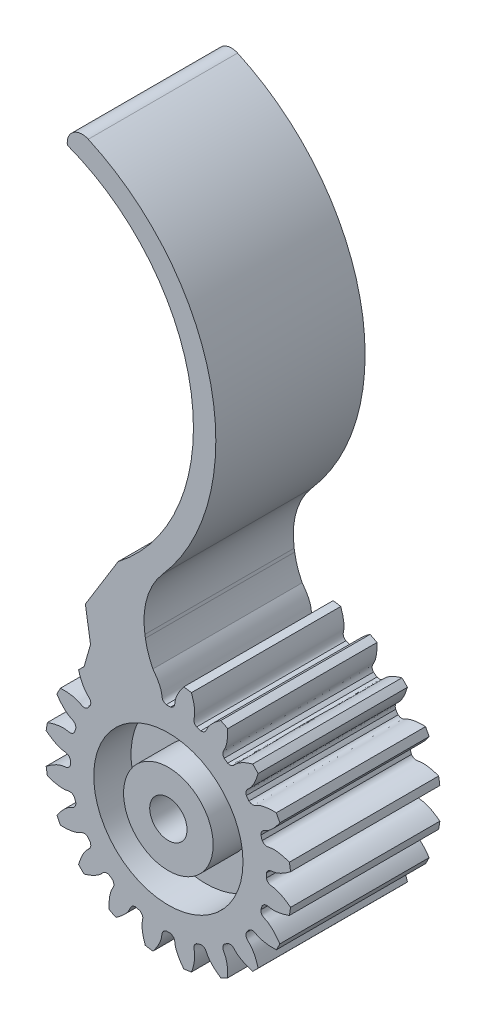
SolidWorks part; units mm, degrees
material "聚脂树脂"
ref_plane "前视基准面" through (0, 0, 0) normal (0, 0, 1) x (1, 0, 0)
ref_plane "上视基准面" through (0, 0, 0) normal (0, 1, 0) x (1, 0, 0)
ref_plane "右视基准面" through (0, 0, 0) normal (1, 0, 0) x (0, 0, -1)
other "Configuration Table"
sketch "草图1" plane through (0, 0, 0) normal (0, 0, 1) x (1, 0, 0)
  circle A0 centre (0, 0) radius 16.5
extrude "凸台-拉伸1" add sketch "草图1" along normal blind 20
ref_axis "基准轴1" through (0, 0, -1.5) along (0, 0, 1)
sketch "草图2" plane through (0, 0, 0) normal (0, 0, 1) x (1, 0, 0)
  line L0 (0, 0) -> (0, 16.5) construction
  circle A0 centre (0, 0) radius 16.5 construction
  arc A1 (0.29, 13.1218) -> (-0.29, 13.1218) centre (0, 0) ccw
  arc A2 (4.7717, 18.7474) -> (-4.7717, 18.7474) centre (0, 0) ccw
  spline S0 degree 3 poles (0.29, 13.1218) (0.9168, 13.3402) (0.8356, 13.7807) (0.9193, 14.205) (0.9283, 14.2463) (0.9395, 14.293) (0.9529, 14.3448) (0.969, 14.4018) (0.9878, 14.4638) (1.0095, 14.5309) (1.0345, 14.6028) (1.0629, 14.6795) (1.0948, 14.7608) (1.1305, 14.8467) (1.1702, 14.9371) (1.2141, 15.0317) (1.2623, 15.1305) (1.315, 15.2334) (1.3725, 15.3401) (1.4349, 15.4506) (1.5023, 15.5646) (1.575, 15.6821) (1.653, 15.8029) (1.7366, 15.9267) (1.826, 16.0534) (1.9211, 16.1829) (2.0223, 16.3149) (2.1296, 16.4493) (2.2432, 16.5859) (2.3632, 16.7244) (2.4897, 16.8646) (2.6229, 17.0065) (2.7628, 17.1496) (2.9095, 17.2939) (3.0632, 17.4391) (3.224, 17.585) (3.3918, 17.7313) (3.567, 17.8779) (3.7493, 18.0245) (3.9391, 18.1709) (4.1363, 18.3167) (4.4122, 18.5125) (4.6259, 18.6545) (4.7717, 18.7474) knots 0 0 0 0 0.165916 0.170906 0.176664 0.183189 0.190482 0.198542 0.207371 0.216967 0.22733 0.238462 0.250361 0.263027 0.276462 0.290664 0.305634 0.321371 0.337876 0.355149 0.37319 0.391998 0.411574 0.431917 0.453028 0.474907 0.497554 0.520968 0.54515 0.570099 0.595817 0.622302 0.649554 0.677575 0.706363 0.735918 0.766242 0.797333 0.829191 0.861818 0.895212 0.929373 1 1 1 1
  spline S1 degree 3 poles (-0.29, 13.1218) (-0.9168, 13.3402) (-0.8356, 13.7807) (-0.9193, 14.205) (-0.9283, 14.2463) (-0.9395, 14.293) (-0.9529, 14.3448) (-0.969, 14.4018) (-0.9878, 14.4638) (-1.0095, 14.5309) (-1.0345, 14.6028) (-1.0629, 14.6795) (-1.0948, 14.7608) (-1.1305, 14.8467) (-1.1702, 14.9371) (-1.2141, 15.0317) (-1.2623, 15.1305) (-1.315, 15.2334) (-1.3725, 15.3401) (-1.4349, 15.4506) (-1.5023, 15.5646) (-1.575, 15.6821) (-1.653, 15.8029) (-1.7366, 15.9267) (-1.826, 16.0534) (-1.9211, 16.1829) (-2.0223, 16.3149) (-2.1296, 16.4493) (-2.2432, 16.5859) (-2.3632, 16.7244) (-2.4897, 16.8646) (-2.6229, 17.0065) (-2.7628, 17.1496) (-2.9095, 17.2939) (-3.0632, 17.4391) (-3.224, 17.585) (-3.3918, 17.7313) (-3.567, 17.8779) (-3.7493, 18.0245) (-3.9391, 18.1709) (-4.1363, 18.3167) (-4.4122, 18.5125) (-4.6259, 18.6545) (-4.7717, 18.7474) knots 0 0 0 0 0.165916 0.170906 0.176664 0.183189 0.190482 0.198542 0.207371 0.216967 0.22733 0.238462 0.250361 0.263027 0.276462 0.290664 0.305634 0.321371 0.337876 0.355149 0.37319 0.391998 0.411574 0.431917 0.453028 0.474907 0.497554 0.520968 0.54515 0.570099 0.595817 0.622302 0.649554 0.677575 0.706363 0.735918 0.766242 0.797333 0.829191 0.861818 0.895212 0.929373 1 1 1 1
extrude "切除-拉伸1" cut sketch "草图2" along normal through all
pattern_circular "阵列(圆周)1" count 20 over 360 about axis through (0, 0, -1.5) along (0, 0, 1) of "切除-拉伸1"
sketch "草图3" plane through (0, 0, 0) normal (0, 0, 1) x (1, 0, 0)
  circle A0 centre (0, 0) radius 15 construction
  dimension "Dn" = 30
sketch "草图4" plane through (0, 0, 20) normal (0, 0, 1) x (1, 0, 0)
  line L0 (0, 0) -> (0, 24.252) construction
  line L1 (0, 0) -> (-4.1504, 26.2048) construction
  line L2 (-14.6667, -3.2847) -> (-22.6322, 47.0071) construction
  line L3 (-2.5812, 16.2969) -> (-3.9432, 24.8963)
  line L4 (-9.8663, 11.4731) -> (-11.763, 23.4486)
  line L5 (-16.5467, 75.4159) -> (-13.5328, 71.4159)
  line L6 (-11.294, 12.029) -> (-10.4295, 15.029)
  line L7 (-3.0932, 16.2075) -> (-2.5812, 16.2969)
  line L8 (0, 0) -> (-34.8237, -5.5155) construction
  arc A2 (-2.0665, 16.3701) -> (-3.0932, 16.2075) centre (0, 0) ccw construction
  circle A4 centre (-22.6411, 47.0635) radius 26 construction
  circle A5 centre (-22.6411, 47.0635) radius 29 construction
  arc A6 (-11.763, 23.4486) -> (-13.5328, 71.4159) centre (-22.6411, 47.0635) ccw
  arc A7 (-3.9432, 24.8963) -> (-16.5467, 75.4159) centre (-22.6411, 47.0635) ccw
  arc A8 (-3.7791, 12.5692) -> (-4.3306, 12.39) centre (0, 0) ccw construction
  arc A9 (-7.024, 14.9303) -> (-7.9502, 14.4584) centre (0, 0) ccw construction
  arc A10 (-7.4782, 10.7862) -> (-7.9474, 10.4453) centre (0, 0) ccw construction
  arc A12 (-3.7791, 12.5692) -> (-4.3306, 12.39) centre (0, 0) ccw
  arc A13 (-7.024, 14.9303) -> (-7.9502, 14.4584) centre (0, 0) ccw
  arc A14 (-7.4782, 10.7862) -> (-7.9474, 10.4453) centre (0, 0) ccw
  spline S0 degree 3 poles (2295.3671, 1929.7263) (-117.6975, -134.774) (-40.8912, 20.8175) (-11.0168, 11.9483) (-10.7713, 11.8675) (-10.4966, 11.7648) (-10.2471, 11.6599) (-10.0224, 11.5547) (-9.822, 11.4509) (-9.671, 11.3649) (-9.5386, 11.2841) (-9.4441, 11.2225) (-9.3578, 11.1623) (-9.3008, 11.1209) (-9.2491, 11.0817) (-9.2026, 11.0451) (-9.1503, 11.0021) (-9.105, 10.9626) (-4.5559, 6.7443) (-24.7562, -23.4769) (1867.2073, 2351.7135) knots -12.160638 -12.160638 -12.160638 -12.160638 0.502446 0.525093 0.568083 0.608002 0.644851 0.678629 0.709336 0.736973 0.749639 0.77267 0.783033 0.792629 0.801458 0.809518 0.816811 0.829094 0.834084 3.350793 3.350793 3.350793 3.350793 only from (-11.294, 12.029) to (-7.9474, 10.4453) construction
  spline S1 degree 3 poles (-3000.2151, -128.3054) (33.5455, 6.2288) (-2.7783, 7.6499) (-3.5171, 13.8097) (-3.5224, 13.8696) (-3.5265, 13.9372) (-3.5289, 13.9963) (-3.5307, 14.0865) (-3.5293, 14.2134) (-3.5206, 14.3824) (-3.5033, 14.5733) (-3.4754, 14.7858) (-3.4352, 15.0192) (-3.381, 15.2729) (-3.3111, 15.5461) (-3.2398, 15.7847) (-3.1737, 15.9845) (7.1936, 45.3178) (178.2143, 16.0013) (-2910.3372, -722.7198) knots -2.350827 -2.350827 -2.350827 -2.350827 0.165916 0.170906 0.183189 0.190482 0.198542 0.207371 0.22733 0.250361 0.276462 0.305634 0.337876 0.37319 0.411574 0.453028 0.474907 0.497554 13.160601 13.160601 13.160601 13.160601 only from (-3.7791, 12.5692) to (-3.0932, 16.2075) construction
  spline S2 degree 3 poles (2779.3421, 1125.9713) (-153.5845, -91.8071) (-32.4569, 32.4347) (-6.7853, 14.7679) (-6.5768, 14.6152) (-6.3474, 14.4326) (-6.1425, 14.2557) (-5.9612, 14.0862) (-5.8028, 13.9257) (-5.6857, 13.7971) (-5.5848, 13.6794) (-5.514, 13.5916) (-5.4504, 13.5077) (-5.409, 13.4507) (-5.3719, 13.3975) (-5.3391, 13.3482) (-5.3027, 13.2912) (-5.2717, 13.2396) (-2.2488, 7.822) (-30.7993, -14.6778) (2502.5391, 1659.6136) knots -12.160638 -12.160638 -12.160638 -12.160638 0.502446 0.525093 0.568083 0.608002 0.644851 0.678629 0.709336 0.736973 0.749639 0.77267 0.783033 0.792629 0.801458 0.809518 0.816811 0.829094 0.834084 3.350793 3.350793 3.350793 3.350793 only from (-7.024, 14.9303) to (-4.3306, 12.39) construction
  spline S3 degree 3 poles (-2813.7256, -1049.1431) (29.9789, 16.29) (-5.0063, 6.4169) (-7.6124, 12.047) (-7.636, 12.1023) (-7.6607, 12.1653) (-7.6812, 12.2208) (-7.7108, 12.3061) (-7.7487, 12.4272) (-7.7927, 12.5905) (-7.8352, 12.7775) (-7.8743, 12.9882) (-7.9082, 13.2226) (-7.9351, 13.4806) (-7.9531, 13.762) (-7.959, 14.011) (-7.9578, 14.2215) (-7.1625, 45.3227) (164.5472, 70.2894) (-2544.5625, -1586.6911) knots -2.350827 -2.350827 -2.350827 -2.350827 0.165916 0.170906 0.183189 0.190482 0.198542 0.207371 0.22733 0.250361 0.276462 0.305634 0.337876 0.37319 0.411574 0.453028 0.474907 0.497554 13.160601 13.160601 13.160601 13.160601 only from (-7.4782, 10.7862) to (-7.9502, 14.4584) construction
  spline S4 degree 3 poles (-3.7791, 12.5692) (-3.2504, 12.9706) (-3.4637, 13.3644) (-3.5171, 13.8097) (-3.5224, 13.8696) (-3.5265, 13.9372) (-3.5289, 13.9963) (-3.5307, 14.0865) (-3.5293, 14.2134) (-3.5206, 14.3824) (-3.5033, 14.5733) (-3.4754, 14.7858) (-3.4352, 15.0192) (-3.381, 15.2729) (-3.3111, 15.5461) (-3.224, 15.8378) (-3.1479, 16.0599) (-3.1017, 16.1848) (-3.0932, 16.2075) knots 0 0 0 0 0.165916 0.170906 0.183189 0.190482 0.198542 0.207371 0.22733 0.250361 0.276462 0.305634 0.337876 0.37319 0.411574 0.453028 0.497554 0.507432 0.507432 0.507432 0.507432
  spline S5 degree 3 poles (-7.024, 14.9303) (-6.9129, 14.8568) (-6.7202, 14.7228) (-6.459, 14.5233) (-6.2419, 14.3433) (-6.0489, 14.1699) (-5.8792, 14.0047) (-5.7318, 13.8492) (-5.6234, 13.7255) (-5.5309, 13.613) (-5.4664, 13.5298) (-5.409, 13.4507) (-5.3719, 13.3975) (-5.3391, 13.3482) (-5.3027, 13.2912) (-5.2717, 13.2396) (-5.0532, 12.848) (-4.9943, 12.404) (-4.3306, 12.39) knots 0.492568 0.492568 0.492568 0.492568 0.546972 0.588426 0.62681 0.662124 0.694366 0.723538 0.749639 0.761538 0.783033 0.792629 0.801458 0.809518 0.816811 0.829094 0.834084 1 1 1 1
  spline S6 degree 3 poles (-7.4782, 10.7862) (-7.0995, 11.3313) (-7.424, 11.64) (-7.6124, 12.047) (-7.636, 12.1023) (-7.6607, 12.1653) (-7.6812, 12.2208) (-7.7108, 12.3061) (-7.7487, 12.4272) (-7.7927, 12.5905) (-7.8352, 12.7775) (-7.8743, 12.9882) (-7.9082, 13.2226) (-7.9351, 13.4806) (-7.9531, 13.762) (-7.9603, 14.0664) (-7.9566, 14.3011) (-7.9513, 14.4342) (-7.9502, 14.4584) knots 0 0 0 0 0.165916 0.170906 0.183189 0.190482 0.198542 0.207371 0.22733 0.250361 0.276462 0.305634 0.337876 0.37319 0.411574 0.453028 0.497554 0.507432 0.507432 0.507432 0.507432
  spline S7 degree 3 poles (-11.294, 12.029) (-11.1656, 11.9934) (-10.9409, 11.9255) (-10.6308, 11.8165) (-10.3687, 11.7125) (-10.1316, 11.6072) (-9.9192, 11.5025) (-9.7309, 11.4002) (-9.5896, 11.316) (-9.4669, 11.2376) (-9.3798, 11.1783) (-9.3008, 11.1209) (-9.2491, 11.0817) (-9.2026, 11.0451) (-9.1503, 11.0021) (-9.105, 10.9626) (-8.7761, 10.6576) (-8.5829, 10.2536) (-7.9474, 10.4453) knots 0.492568 0.492568 0.492568 0.492568 0.546972 0.588426 0.62681 0.662124 0.694366 0.723538 0.749639 0.761538 0.783033 0.792629 0.801458 0.809518 0.816811 0.829094 0.834084 1 1 1 1
  dimension "D6" = 52
  dimension "D7" = 48
  dimension "D5" = 58
  dimension "D1" = 9
  dimension "D2" = 15
  dimension "D3" = 7.95
  dimension "D4" = 25
  dimension "D8" = 4
  dimension "D9" = 3
extrude "凸台-拉伸2" add sketch "草图4" against normal blind 20 contours L4 S7 A14 S6 A13 S5 A12 S4 L7 L3 A7 L5 A6 | L6 S7 L4 region at (-2.9558, 16.9313, 20) region at (-10.5293, 12.8632, 20)
fillet "圆角1" radius 10 1 edges
fillet "圆角2" radius 2 1 edges at (-16.5467, 75.4159, 10)
fillet "圆角4" radius 10 1 edges at (-3.9432, 24.8963, 10)
sketch "草图5" plane through (0, 0, 20) normal (0, 0, 1) x (1, 0, 0)
  circle A0 centre (0, 0) radius 2.5
  dimension "D1" = 5
extrude "切除-拉伸2" cut sketch "草图5" against normal blind 20
chamfer "倒角1" distance 5 angle 45 1 edges at (-11.763, 23.4486, 10) first distance on face at (-11.0962, 19.2388, 10)
sketch "草图6" plane through (0, 0, 20) normal (0, 0, 1) x (1, 0, 0)
  line L1 (-6.7321, 26.4989) -> (-11.1191, 19.3832)
  line L2 (-11.1191, 19.3832) -> (-3.1432, 19.8453)
  arc A0 (-0.7983, 27.9876) -> (-10.7289, 73.504) centre (-22.6411, 47.0635) ccw construction
  arc A1 (-6.7321, 26.4989) -> (-13.5328, 71.4159) centre (-22.6411, 47.0635) ccw construction
  arc A2 (-10.7289, 73.504) -> (-13.5328, 71.4159) centre (-11.5504, 71.6805) ccw construction
  arc A3 (-0.7983, 27.9876) -> (-10.7289, 73.504) centre (-22.6411, 47.0635) ccw
  arc A4 (-6.7321, 26.4989) -> (-13.5328, 71.4159) centre (-22.6411, 47.0635) ccw
  arc A5 (-10.7289, 73.504) -> (-13.5328, 71.4159) centre (-11.5504, 71.6805) ccw
  arc A6 (-0.7983, 27.9876) -> (-3.1432, 19.8453) centre (6.7337, 21.4096) ccw construction
  arc A7 (-0.7983, 27.9876) -> (-3.1432, 19.8453) centre (6.7337, 21.4096) ccw
sketch "草图7" plane through (0, 0, 0) normal (0, 0, -1) x (-1, 0, 0)
  circle A0 centre (0, 0) radius 10
  dimension "D1" = 20
extrude "切除-拉伸3" cut sketch "草图7" against normal blind 3
sketch "草图8" plane through (0, 0, 20) normal (0, 0, 1) x (1, 0, 0)
  circle A0 centre (0, 0) radius 6
  circle A1 centre (0, 0) radius 10
  dimension "D1" = 12
  dimension "D2" = 20
extrude "切除-拉伸4" cut sketch "草图8" against normal blind 5
